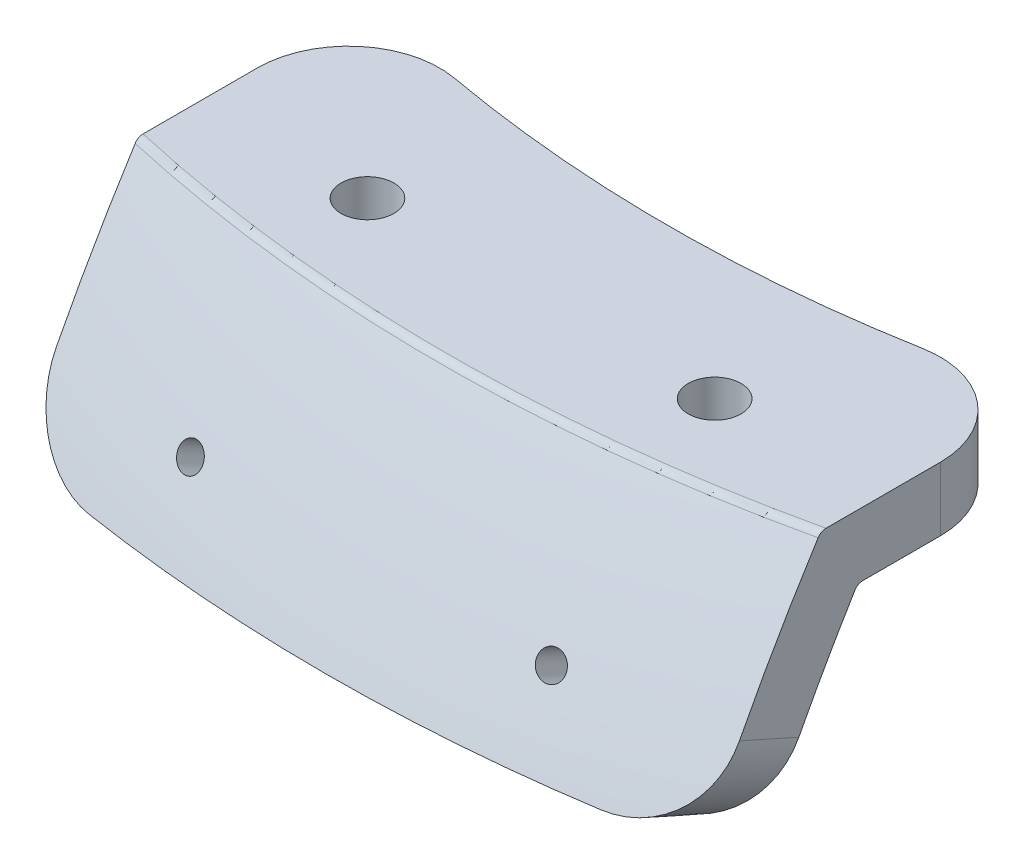
SolidWorks part; units mm, degrees
material "Polyether Polyol"
ref_plane "Front Plane" through (0, 0, 0) normal (0, 0, 1) x (1, 0, 0)
ref_plane "Top Plane" through (0, 0, 0) normal (0, 1, 0) x (1, 0, 0)
ref_plane "Right Plane" through (0, 0, 0) normal (1, 0, 0) x (0, 0, -1)
sketch "Sketch1" plane through (0, 0, 0) normal (1, 0, 0) x (0, 0, -1)
  line L0 (-182.3577, 142.3626) -> (-175.976, 139.4862) construction
  line L1 (-169.6296, 166.1688) -> (-144.7872, 166.1688) construction
  line L9 (-144.7872, 166.1688) -> (-144.7872, 159.1688) construction
  line L10 (-144.7872, 159.1688) -> (-165.7041, 159.1688) construction
  line L11 (-182.3577, 142.3626) -> (-175.976, 139.4862)
  line L12 (-169.6296, 166.1688) -> (-144.7872, 166.1688)
  line L13 (-144.7872, 166.1688) -> (-144.7872, 159.1688)
  line L14 (-144.7872, 159.1688) -> (-165.7041, 159.1688)
  line L15 (0, 0) -> (0, 60.1698) construction
  arc A5 (-165.7041, 159.1688) -> (-175.976, 139.4862) centre (0, 60.1698) ccw construction
  arc A6 (-169.6296, 166.1688) -> (-182.3577, 142.3626) centre (0, 60.1698) ccw construction
  arc A7 (-165.7041, 159.1688) -> (-175.976, 139.4862) centre (0, 60.1698) ccw
  arc A8 (-169.6296, 166.1688) -> (-182.3577, 142.3626) centre (0, 60.1698) ccw
revolve "Revolve1" add sketch "Sketch1" angle 30 mid plane about L15
sketch "Sketch2" plane through (0, 0, 0) normal (-1, 0, 0) x (0, 0, 1)
  line L0 (0, 60.1698) -> (171.9865, 147.8013) construction
  line L3 (0, -200000) -> (0, 218797.9879) construction
  arc A0 (175.976, 139.4862) -> (165.7041, 159.1688) centre (0, 60.1698) ccw construction
  dimension "D1" = 63
ref_plane "Plane1" through (0, 47.7683, -24.3392) normal (0, -0.891, 0.454) x (0, 0.454, 0.891)
sketch "Sketch4" plane through (0, 47.7683, -24.3392) normal (0, -0.891, 0.454) x (0, 0.454, 0.891)
  line L0 (200.4524, 17.5373) -> (239.1484, 20.9228) construction
  line L1 (200.3217, 19.0316) -> (239.0177, 22.4171)
  line L2 (200.3217, 19.0316) -> (200.4524, 17.5373)
  line L3 (27.3165, 0) -> (220.3415, 0) construction
  line L4 (200.4524, 17.5373) -> (239.1484, 20.9228)
  line L5 (239.0177, 22.4171) -> (239.1484, 20.9228)
  dimension "D1" = 3
  dimension "D2" = 5
revolve "Cut-Revolve1" cut sketch "Sketch4" angle 360 about L0
mirror "Mirror1" about plane through (0, 0, 0) normal (1, 0, 0) of "Cut-Revolve1"
sketch "Sketch5" plane through (0, 0, 0) normal (0, 1, 0) x (1, 0, 0)
  line L1 (37.4737, -139.8537) -> (-37.4737, -139.8537)
  line L2 (37.4737, -139.8537) -> (37.4737, -182.3577)
  line L3 (37.4737, -182.3577) -> (-37.4737, -182.3577)
  line L4 (-37.4737, -139.8537) -> (-37.4737, -182.3577)
  arc A0 (-47.1977, -176.1441) -> (47.1977, -176.1441) centre (0, 0) ccw construction
extrude "Cut-Extrude2" cut sketch "Sketch5" along normal through all flip side to cut
fillet "Fillet1" radius 10 4 edges at (-37.4737, 162.6688, 139.8537) (37.4737, 162.6688, 139.8537)
fillet "Fillet2" radius 1 2 edges at (0, 166.1688, 169.6296) (0, 159.1688, 165.7041)
sketch "Sketch6" plane through (0, 166.1688, 0) normal (0, 1, 0) x (1, 0, 0)
  circle A0 centre (19.05, -158.6742) radius 2.9 construction
  circle A1 centre (-19.05, -158.6742) radius 2.9 construction
  circle A2 centre (19.05, -158.6742) radius 2.9
  circle A3 centre (-19.05, -158.6742) radius 2.9
extrude "Cut-Extrude3" cut sketch "Sketch6" against normal through all
